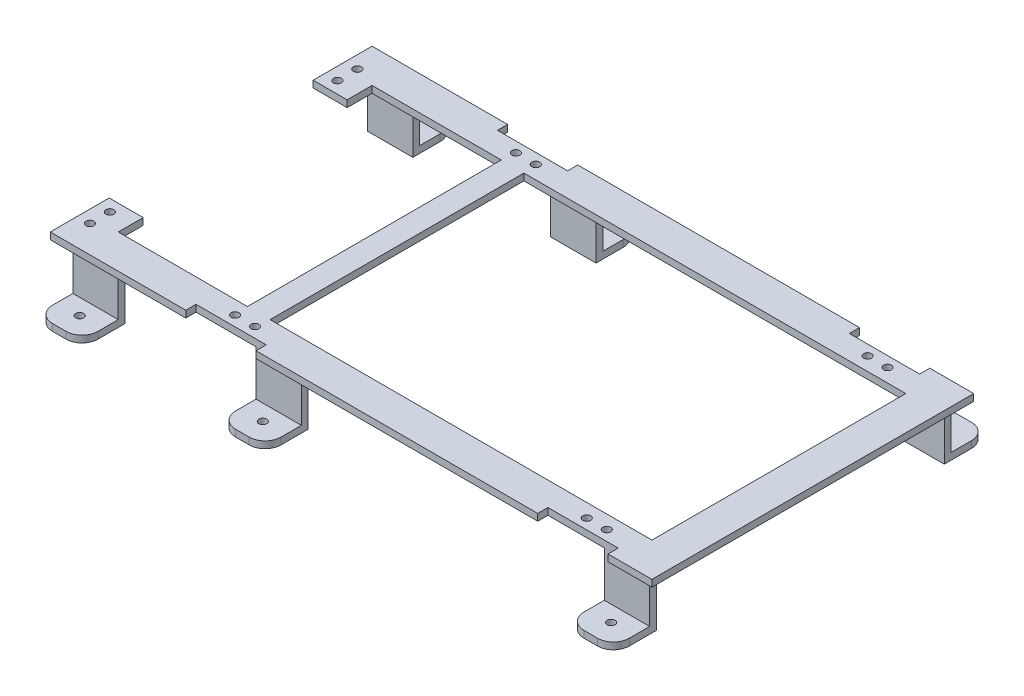
SolidWorks part; units mm, degrees
ref_plane "Alzado" through (0, 0, 0) normal (0, 0, 1) x (1, 0, 0)
ref_plane "Planta" through (0, 0, 0) normal (0, 1, 0) x (1, 0, 0)
ref_plane "Vista lateral" through (0, 0, 0) normal (1, 0, 0) x (0, 0, -1)
sketch "Croquis1" plane through (0, 0, 0) normal (0, 1, 0) x (1, 0, 0)
  line L0 (117.75, 56) -> (-117.75, 56)
  line L1 (132.75, -71) -> (-132.75, -71)
  line L2 (132.75, -71) -> (132.75, 71)
  line L3 (132.75, 71) -> (-132.75, 71)
  line L4 (-132.75, -71) -> (-132.75, 71)
  line L5 (132.75, -71) -> (-132.75, 71) construction
  line L6 (132.75, 71) -> (-132.75, -71) construction
  line L7 (-117.75, -56) -> (-117.75, 56)
  line L8 (117.75, -56) -> (-117.75, -56)
  line L9 (117.75, -56) -> (117.75, 56)
  point P0 (0, 0)
  dimension "D1" = 142
  dimension "D2" = 265.5
  dimension "D3" = 15
extrude "Saliente-Extruir1" add sketch "Croquis1" along normal blind 3
ref_plane "Plano1" through (-127.25, 0, 0) normal (1, 0, 0) x (0, 0, -1)
sketch "Croquis2" plane through (-127.25, 0, 0) normal (-1, 0, 0) x (0, 0, 1)
  line L0 (66.5, 0) -> (66.5, -20)
  line L6 (63.5, 0) -> (66.5, 0)
  line L8 (82.5, -23) -> (82.5, -20)
  line L9 (82.5, -20) -> (66.5, -20)
  line L20 (63.5, 0) -> (63.5, -23)
  line L21 (63.5, -23) -> (82.5, -23)
  line L22 (71, 3) -> (71, 0) construction
  line L23 (-71, 0) -> (71, 0) construction
  dimension "D1" = 23
  dimension "D2" = 3
  dimension "D3" = 4.5
  dimension "D4" = 19
  dimension "D5" = 3
extrude "Saliente-Extruir2" add sketch "Croquis2" against normal blind 20
mirror "Simetría1" about plane through (0, 0, 0) normal (1, 0, 0) of "Saliente-Extruir2"
mirror "Simetría2" about plane through (0, 0, 0) normal (0, 0, 1) of "Simetría1"
sketch "Croquis3" plane through (0, 3, 0) normal (0, 1, 0) x (1, 0, 0)
  line L1 (-120, 32.5) -> (-60, 32.5)
  line L2 (-120, 32.5) -> (-120, -32.5)
  line L3 (-120, -32.5) -> (-60, -32.5)
  line L4 (-60, 32.5) -> (-60, -32.5)
  point P4 (-60, 0)
  dimension "D1" = 65
  dimension "D2" = 60
  dimension "D3" = 60
extrude "Cortar-Extruir1" [suppressed] cut sketch "Croquis3" against normal through all
mirror "Simetría3" [suppressed] about plane through (0, 0, 0) normal (1, 0, 0)
ref_plane "Plano2" through (-36.45, 0, 0) normal (1, 0, 0) x (0, 0, -1)
sketch "Croquis4" plane through (-36.45, 0, 0) normal (1, 0, 0) x (0, 0, -1)
  line L12 (-63.5, 0) -> (-66.5, 0)
  line L13 (-66.5, 0) -> (-66.5, -20)
  line L14 (-66.5, -20) -> (-82.5, -20)
  line L15 (-82.5, -20) -> (-82.5, -23)
  line L16 (-82.5, -23) -> (-63.5, -23)
  line L17 (-82.5, -23) -> (-63.5, -23)
  line L19 (-66.5, 0) -> (-66.5, -20)
  line L20 (-66.5, -20) -> (-82.5, -20)
  line L21 (-82.5, -20) -> (-82.5, -23)
  line L28 (-63.5, 0) -> (-66.5, 0)
  line L38 (-63.5, -23) -> (-63.5, 0)
  line L40 (-63.5, -23) -> (-63.5, 0)
  dimension "D1" = 0
extrude "Saliente-Extruir3" add sketch "Croquis4" along normal mid plane 20
mirror "Simetría4" about plane through (0, 0, 0) normal (0, 0, 1) of "Saliente-Extruir3"
sketch "Croquis5" plane through (0, 3, 0) normal (0, 1, 0) x (1, 0, 0)
  line L1 (-105.499, -45) -> (-143.7054, -45)
  line L2 (-105.499, -45) -> (-105.499, 45)
  line L3 (-105.499, 45) -> (-143.7054, 45)
  line L4 (-143.7054, -45) -> (-143.7054, 45)
  line L5 (-105.499, -45) -> (-143.7054, 45) construction
  line L6 (-105.499, 45) -> (-143.7054, -45) construction
  point P0 (-124.6022, 0)
  dimension "D1" = 90
extrude "Cortar-Extruir2" cut sketch "Croquis5" against normal through all
sketch "Croquis7" plane through (0, 3, 0) normal (0, 1, 0) x (1, 0, 0)
  line L1 (-49.2, 56) -> (-23.2245, 56)
  line L2 (-49.2, 56) -> (-49.2, -56)
  line L3 (-49.2, -56) -> (-23.2245, -56)
  line L4 (-23.2245, 56) -> (-23.2245, -56)
extrude "Cortar-Extruir3" [suppressed] cut sketch "Croquis7" against normal through all
sketch "Croquis6" plane through (0, 3, 0) normal (0, 1, 0) x (1, 0, 0)
  line L0 (-55.75, 56) -> (-55.75, -56) construction
  line L1 (117.75, 56) -> (-117.75, 56) construction
  line L2 (-117.75, -56) -> (117.75, -56) construction
  line L4 (-132.75, -45) -> (-132.75, -71) construction
  line L6 (-60.75, 56) -> (-50.75, 56)
  line L7 (-60.75, 56) -> (-60.75, -56)
  line L8 (-60.75, -56) -> (-50.75, -56)
  line L9 (-50.75, 56) -> (-50.75, -56)
  point P12 (-55.75, 56)
  point P13 (-55.75, -56)
  dimension "D1" = 77
  dimension "D2" = 10
extrude "Saliente-Extruir4" add sketch "Croquis6" against normal up to surface (3 mm away) up to face at (-36.45, 0, -65)
sketch "Croquis8" plane through (0, 3, 0) normal (0, 1, 0) x (1, 0, 0)
  line L0 (132.75, 71) -> (-132.75, 71) construction
  line L1 (113.35, 66.5) -> (82.35, 66.5)
  line L2 (113.35, 66.5) -> (113.35, 71)
  line L3 (113.35, 71) -> (82.35, 71)
  line L4 (82.35, 66.5) -> (82.35, 71)
  line L5 (132.75, -71) -> (132.75, 71) construction
  line L6 (-132.75, 71) -> (-132.75, 45) construction
  line L7 (-41.95, 66.5) -> (-72.95, 66.5)
  line L8 (-41.95, 66.5) -> (-41.95, 71)
  line L9 (-41.95, 71) -> (-72.95, 71)
  line L10 (-72.95, 66.5) -> (-72.95, 71)
  dimension "D1" = 4.5
  dimension "D2" = 19.4
  dimension "D3" = 31
  dimension "D4" = 59.8
extrude "Cortar-Extruir4" cut sketch "Croquis8" against normal up to surface (3 mm away) up to face at (-71.5, 0, 0)
sketch "Croquis9" plane through (0, 3, 0) normal (0, 1, 0) x (1, 0, 0)
  circle A0 centre (-127.25, 59) radius 1.75
  circle A1 centre (-127.25, 50.2) radius 1.75
extrude "Cortar-Extruir5" cut sketch "Croquis9" against normal through all
sketch "Croquis11" plane through (0, 3, 0) normal (0, 1, 0) x (1, 0, 0)
  circle A0 centre (103.7509, 61.953) radius 1.75
  circle A1 centre (94.9509, 61.953) radius 1.75
extrude "Cortar-Extruir7" cut sketch "Croquis11" against normal blind 4
sketch "Croquis12" plane through (0, 3, 0) normal (0, 1, 0) x (1, 0, 0)
  circle A0 centre (-51.4491, 61.953) radius 1.75
  circle A1 centre (-60.2491, 61.953) radius 1.75
  dimension "D1" = 3.5
extrude "Cortar-Extruir8" cut sketch "Croquis12" against normal blind 4
mirror "Simetría5" about plane through (0, 0, 0) normal (0, 0, 1) of "Cortar-Extruir8", "Cortar-Extruir7", "Cortar-Extruir5"
mirror "Simetría6" about plane through (0, 0, 0) normal (0, 0, 1) of "Cortar-Extruir4"
fillet "Redondeo1" radius 7 2 edges at (-127.25, -21.5, 82.5) (-107.25, -21.5, 82.5)
fillet "Redondeo2" radius 7 4 edges at (-26.45, -21.5, 82.5) (-46.45, -21.5, 82.5) (127.25, -21.5, 82.5) (107.25, -21.5, 82.5)
sketch "Croquis13" plane through (0, -20, 0) normal (0, 1, 0) x (1, 0, 0)
  line L0 (-114.25, -82.5) -> (-120.25, -82.5) construction
  line L1 (-127.25, -75.5) -> (-127.25, -66.5) construction
  circle A0 centre (-117.25, -73.5) radius 1.75
  dimension "D2" = 3.5
  dimension "D1" = 9
  dimension "D3" = 10
extrude "Cortar-Extruir9" cut sketch "Croquis13" against normal through all
mirror "Simetría7" about plane through (0, 0, 0) normal (1, 0, 0) of "Cortar-Extruir9"
sketch "Croquis15" plane through (0, -20, 0) normal (0, 1, 0) x (1, 0, 0)
  line L0 (-46.45, -66.5) -> (-46.45, -75.5) construction
  line L1 (-33.45, -82.5) -> (-39.45, -82.5) construction
  circle A0 centre (-36.45, -73.5) radius 1.75
  dimension "D3" = 3.5
  dimension "D1" = 10
  dimension "D2" = 9
extrude "Cortar-Extruir10" cut sketch "Croquis15" against normal through all
mirror "Simetría12" about plane through (0, 0, 0) normal (0, 0, 1) of "Cortar-Extruir10", "Simetría7", "Cortar-Extruir9"
fillet "Redondeo3" radius 7 6 edges at (-127.25, -21.5, -82.5) (-107.25, -21.5, -82.5) (-46.45, -21.5, -82.5) (-26.45, -21.5, -82.5) (107.25, -21.5, -82.5) (127.25, -21.5, -82.5)
